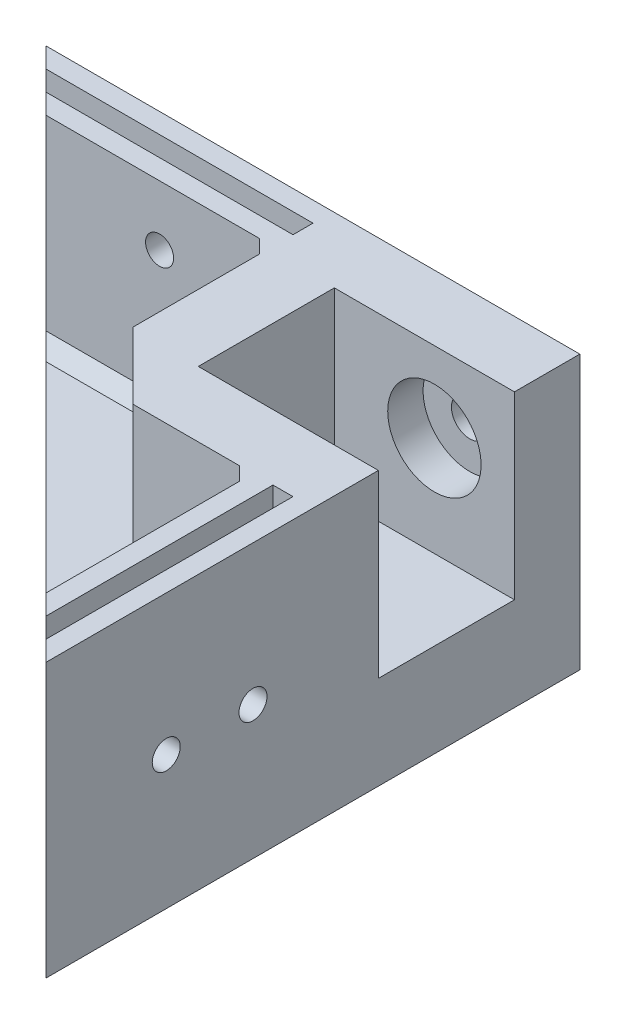
SolidWorks part; units mm, degrees
other "Uwaga1"
sketch "Szkic15" plane through (-43, 30, 80) normal (-0.0864, 0.996, 0.0215) x (0.004, 0.022, -0.9998)
material "ABS"
ref_plane "Płaszczyzna przednia" through (0, 0, 0) normal (0, 0, 1) x (1, 0, 0)
ref_plane "Płaszczyzna górna" through (0, 0, 0) normal (0, 1, 0) x (1, 0, 0)
ref_plane "Płaszczyzna prawa" through (0, 0, 0) normal (1, 0, 0) x (0, 0, -1)
sketch "Szkic1" plane through (0, 0, 0) normal (0, 0, 1) x (1, 0, 0)
  line L1 (0, 0) -> (37, 0)
  line L2 (0, 0) -> (0, 30)
  line L3 (0, 30) -> (37, 30)
  line L4 (37, 0) -> (37, 30)
  dimension "D1" = 37
  dimension "D2" = 30
extrude "Dodanie-wyciągnięcie1" add sketch "Szkic1" along normal blind 40
sketch "Szkic2" plane through (0, 30, 0) normal (0, 1, 0) x (1, 0, 0)
  line L0 (37, -40) -> (37, 0) construction
  line L1 (37, -9.8) -> (10, -9.8)
  line L2 (37, -9.8) -> (37, -30.2)
  line L3 (37, -30.2) -> (10, -30.2)
  line L4 (10, -9.8) -> (10, -30.2)
  line L5 (37, -40) -> (0, -40) construction
  line L6 (37, 0) -> (0, 0) construction
  dimension "D1" = 9.8
  dimension "D2" = 9.8
  dimension "D3" = 27
extrude "Wytnij-wyciągnięcie1" cut sketch "Szkic2" against normal blind 30
ref_plane "Płaszczyzna1" through (0, 0, 20) normal (0, 0, 1) x (1, 0, 0)
sketch "Szkic3" plane through (0, 0, 20) normal (0, 0, 1) x (1, 0, 0)
  line L1 (10, 0) -> (10, 30) construction
  line L2 (10, 0) -> (10, 30)
  line L5 (37, 0) -> (37, 30) construction
  line L6 (37, 30) -> (0, 30) construction
  circle A0 centre (25, 18) radius 7
  dimension "D1" = 14
  dimension "D2" = 12
  dimension "D3" = 12
extrude "Wytnij-wyciągnięcie2" cut sketch "Szkic3" against normal blind 15.5 and the other way blind 15.5 contours A0
sketch "Szkic4" plane through (0, 0, 0) normal (0, 0, -1) x (-1, 0, 0)
  circle A0 centre (-25, 18) radius 7 construction
  circle A1 centre (-25, 18) radius 7 construction
  circle A2 centre (-25, 18) radius 2.75
  dimension "D1" = 5.5
extrude "Wytnij-wyciągnięcie3" cut sketch "Szkic4" against normal through all
sketch "Szkic5" plane through (0, 0, 0) normal (0, -1, 0) x (1, 0, 0)
  line L1 (10, 30.2) -> (37, 30.2)
  line L2 (10, 30.2) -> (10, 9.8)
  line L3 (10, 9.8) -> (37, 9.8)
  line L4 (37, 30.2) -> (37, 9.8)
extrude "Dodanie-wyciągnięcie2" add sketch "Szkic5" against normal blind 3
sketch "Szkic6" plane through (0, 0, 0) normal (0, -1, 0) x (1, 0, 0)
  line L0 (37, 0) -> (-43, 0)
  line L1 (37, 0) -> (37, 80)
  line L2 (-43, 0) -> (37, 80)
  dimension "D1" = 80
extrude "Dodanie-wyciągnięcie3" add sketch "Szkic6" along normal blind 10
ref_plane "Płaszczyzna2" through (0, 0, 80) normal (0, 0, -1) x (-1, 0, 0)
sketch "Szkic8" plane through (0, 0, 80) normal (0, 0, -1) x (-1, 0, 0)
  line L0 (43, -10) -> (-37, -10) construction
  line L1 (40, -3.5) -> (-34, -3.5)
  line L2 (40, -3.5) -> (40, -6.5)
  line L3 (40, -6.5) -> (-34, -6.5)
  line L4 (-34, -3.5) -> (-34, -6.5)
  line L5 (43, 0) -> (0, 0) construction
  line L6 (43, -10) -> (43, 0) construction
  line L7 (-37, -10) -> (-37, 30) construction
  dimension "D1" = 3.5
  dimension "D2" = 3.5
  dimension "D3" = 3
  dimension "D4" = 3
extrude "Wytnij-wyciągnięcie4" cut sketch "Szkic8" along direction (0, 0, -1) on the side of the normal blind 77 contours L1 L4 L3 L2 region at (-3, -5, 80)
sketch "Szkic9" plane through (0, 0, 0) normal (0, 1, 0) x (1, 0, 0)
  line L0 (0, 0) -> (-43, 0)
  line L1 (0, 0) -> (0, -3)
  line L2 (0, -40) -> (0, 0) construction
  line L3 (0, -3) -> (-40, -3)
  line L4 (-40, -3) -> (-43, 0)
  line L5 (0, -6) -> (0, -9)
  line L6 (0, -40) -> (0, 0) construction
  line L7 (0, -9) -> (-34, -9)
  line L8 (37, -80) -> (-43, 0) construction
  line L9 (0, -6) -> (-37, -6)
  line L10 (-37, -6) -> (-34, -9)
  dimension "D1" = 3
  dimension "D2" = 3
  dimension "D3" = 3
extrude "Dodanie-wyciągnięcie4" add sketch "Szkic9" along normal up to surface (30 mm away) up to face at (21, 30, 20)
sketch "Szkic10" plane through (0, 0, 0) normal (0, 1, 0) x (1, 0, 0)
  line L0 (37, -40) -> (37, -80)
  line L1 (37, -40) -> (34, -40)
  line L2 (37, -40) -> (0, -40) construction
  line L3 (34, -40) -> (34, -77)
  line L4 (37, -80) -> (-34, -9) construction
  line L5 (34, -77) -> (37, -80)
  line L6 (31, -40) -> (31, -74)
  line L7 (0, -40) -> (37, -40) construction
  line L8 (31, -40) -> (28, -40)
  line L9 (28, -40) -> (28, -71)
  line L10 (28, -71) -> (31, -74)
  line M4 (-34, -9) -> (37, -80)
  line M5 (37, -80) -> (37, -40)
  line M6 (37, -40) -> (0, -40)
  dimension "D1" = 3
  dimension "D2" = 3
  dimension "D3" = 3
extrude "Dodanie-wyciągnięcie5" add sketch "Szkic10" along direction (0, -1, 0) on the side of the normal up to surface (30 mm away) contours L9 L6 M6 M4 | L3 M6 M4 M5 region at (35.5195, 0, 59.2597) region at (29.5231, 0, 56.2615) up to face at (1, 30, 14)
sketch "Szkic11" plane through (0, 0, 0) normal (0, 1, 0) x (1, 0, 0)
  line L0 (-34, -9) -> (0, -9) construction
  line L1 (0, -40) -> (0, -9) construction
  line L2 (0, -40) -> (28, -40) construction
  line L3 (28, -40) -> (28, -71) construction
  circle A0 centre (-7, -16) radius 2.1
  circle A1 centre (21, -47) radius 3.1
  dimension "D5" = 4.2
  dimension "D6" = 6.2
  dimension "D1" = 7
  dimension "D2" = 7
  dimension "D3" = 7
  dimension "D4" = 7
extrude "Wytnij-wyciągnięcie5" cut sketch "Szkic11" against normal blind 77
sketch "Szkic12" plane through (0, 0, 9) normal (0, 0, 1) x (1, 0, 0)
  line L2 (-34, 30) -> (-34, 0) construction
  line L3 (-34, 0) -> (0, 0) construction
  line L4 (0, 30) -> (-34, 30) construction
  circle A0 centre (-17, 21) radius 2.1
  circle A1 centre (-17, 9) radius 2.1
  dimension "D1" = 4.2
  dimension "D2" = 17
  dimension "D3" = 9
  dimension "D4" = 9
extrude "Wytnij-wyciągnięcie6" cut sketch "Szkic12" against normal blind 77
chamfer "Sfazowanie2" distance 10 angle 45 1 edges at (0, 15, 40)
chamfer "Sfazowanie3" distance 2 angle 45 7 edges at (28, 0, 55.5) (28, 15, 40) (19, 0, 40) (5, 0, 35) (0, 0, 19.5) (-17, 0, 9) (0, 15, 9)
sketch "Szkic13" plane through (28, 0, 0) normal (-1, 0, 0) x (0, 0, 1)
  line L0 (40, 2) -> (40, 15.4383) construction
  line L1 (71, 30) -> (71, 2) construction
  line L2 (69, 0) -> (42, 0) construction
  circle A0 centre (48.9958, 9) radius 2.1
  circle A1 centre (62, 9) radius 2.1
  dimension "D4" = 4.2
  dimension "D1" = 8.9958
  dimension "D2" = 9
  dimension "D3" = 9
extrude "Wytnij-wyciągnięcie7" cut sketch "Szkic13" against normal blind 77
sketch "Szkic14" plane through (0, -10, 0) normal (0, -1, 0) x (1, 0, 0)
  line L3 (37, 0) -> (37, 80)
  line L4 (37, 80) -> (-43, 0)
  line L5 (-43, 0) -> (37, 0)
  line L6 (37, 0) -> (37, 80)
  line L7 (37, 80) -> (-43, 0)
  line L8 (-43, 0) -> (37, 0)
  circle A0 centre (21, 47) radius 3.1 construction
  circle A1 centre (-7, 16) radius 2.1 construction
  circle A2 centre (21, 47) radius 3.1
  circle A3 centre (-7, 16) radius 2.1
  dimension "D1" = 0
extrude "Dodanie-wyciągnięcie6" add sketch "Szkic14" along normal blind 1
